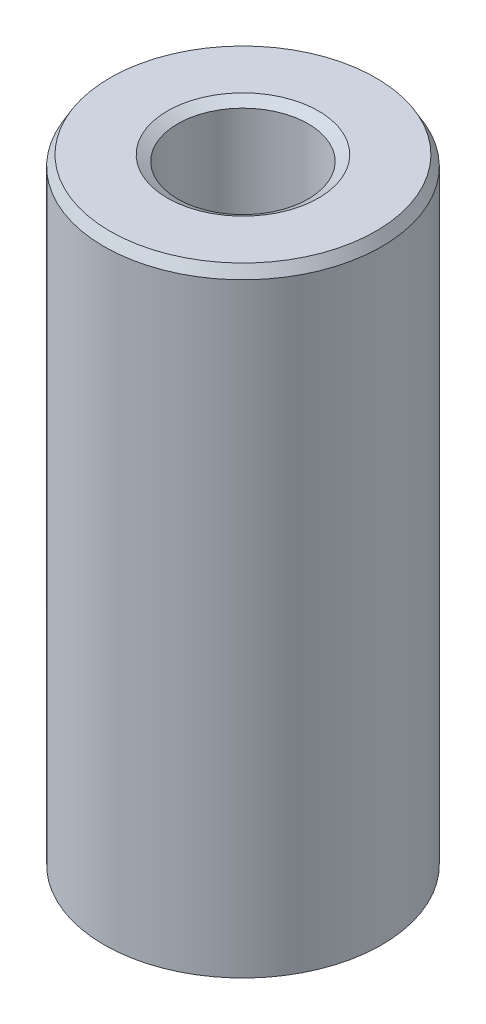
SolidWorks part; units mm, degrees
ref_plane "Front Plane" through (0, 0, 0) normal (0, 0, 1) x (1, 0, 0)
ref_plane "Top Plane" through (0, 0, 0) normal (0, 1, 0) x (1, 0, 0)
ref_plane "Right Plane" through (0, 0, 0) normal (1, 0, 0) x (0, 0, -1)
sketch "Sketch1" plane through (0, 0, 0) normal (0, 1, 0) x (1, 0, 0)
  circle A0 centre (0, 0) radius 22.5
  dimension "SLEEVE_OD" = 45
extrude "Boss-Extrude1" add sketch "Sketch1" along normal blind 100.613
sketch "Sketch2" plane through (0, 0, 0) normal (0, 1, 0) x (1, 0, 0)
  circle A0 centre (0, 0) radius 10.5702
  dimension "BORE_D" = 21.1404
extrude "Cut-Extrude1" cut sketch "Sketch2" along normal through all
chamfer "Chamfer1" distance 1.6702 angle 30 4 edges at (0, 100.613, 10.5702) (0, 0, 10.5702) (0, 0, 22.5) (0, 100.613, 22.5) first distance on face at (0, 100.613, 10.5702) first distance on face at (0, 0, 10.5702) first distance on face at (0, 100.613, 22.5)
